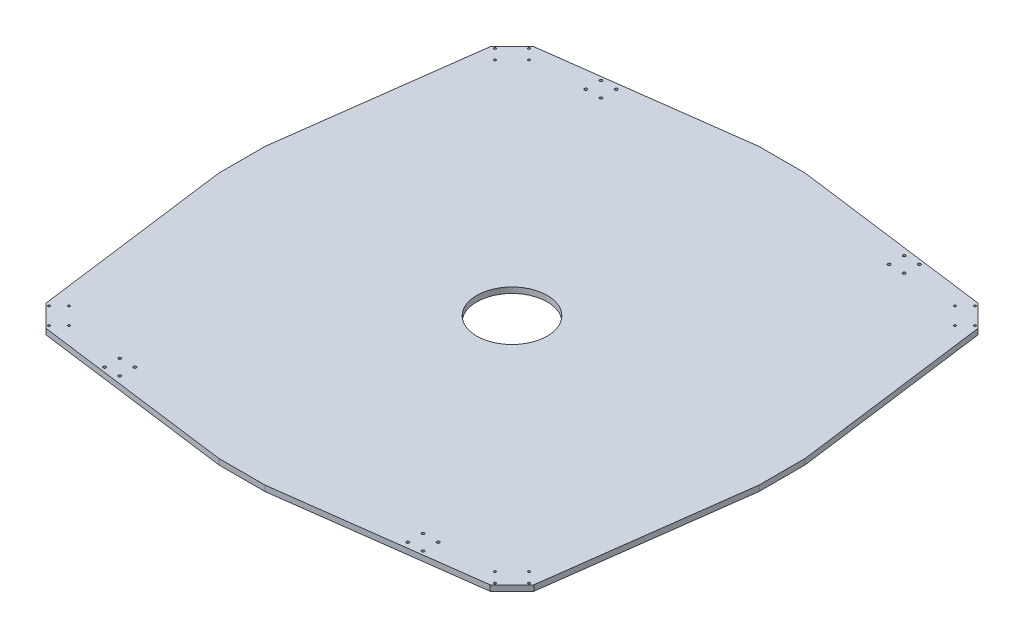
SolidWorks part; units mm, degrees
ref_plane "前视基准面" through (0, 0, 0) normal (0, 0, 1) x (1, 0, 0)
ref_plane "上视基准面" through (0, 0, 0) normal (0, 1, 0) x (1, 0, 0)
ref_plane "右视基准面" through (0, 0, 0) normal (1, 0, 0) x (0, 0, -1)
other "Configuration Table"
sketch "草图1" plane through (0, 0, 0) normal (0, 1, 0) x (1, 0, 0)
  line L0 (-314.9222, 345.9222) -> (-345.9222, 314.9222)
  line L5 (325, -325) -> (-325, 325) construction
  line L6 (325, 325) -> (-325, -325) construction
  line L7 (0, 325) -> (0, -325) construction
  line L8 (-325, 0) -> (325, 0) construction
  line L9 (314.9222, 345.9222) -> (32.7201, 383.0748)
  line L10 (314.9222, 345.9222) -> (345.9222, 314.9222)
  line L12 (-314.9222, 345.9222) -> (-32.7201, 383.0748)
  line L13 (0, 325) -> (0, 399.6983)
  line L14 (-32.7201, 383.0748) -> (32.7201, 383.0748)
  line L15 (314.9222, -345.9222) -> (32.7201, -383.0748)
  line L16 (-32.7201, -383.0748) -> (32.7201, -383.0748)
  line L17 (-314.9222, -345.9222) -> (-32.7201, -383.0748)
  line L18 (-314.9222, -345.9222) -> (-345.9222, -314.9222)
  line L19 (-345.9222, 314.9222) -> (-383.0748, 32.7201)
  line L20 (-383.0748, -32.7201) -> (-383.0748, 32.7201)
  line L21 (-345.9222, -314.9222) -> (-383.0748, -32.7201)
  line L22 (-345.9222, -314.9222) -> (-314.9222, -345.9222)
  line L23 (345.9222, -314.9222) -> (314.9222, -345.9222)
  line L24 (345.9222, -314.9222) -> (383.0748, -32.7201)
  line L25 (383.0748, 32.7201) -> (383.0748, -32.7201)
  line L26 (345.9222, 314.9222) -> (383.0748, 32.7201)
  line L27 (-337.8712, -313.8296) -> (-342.443, -318.4014)
  line L28 (-314.9222, -345.9222) -> (-293.6978, -324.6978)
  line L29 (-326.1795, -302.1379) -> (-298.6587, -329.6587)
  line L30 (-345.9222, -314.9222) -> (-325, -294)
  line L31 (-326.1795, -302.1379) -> (-329.6587, -298.6587)
  line L32 (-313.4871, -289.4455) -> (-337.8712, -313.8296)
  line L33 (-289.4455, -313.4871) -> (-313.8296, -337.8712)
  line L34 (-313.8296, -337.8712) -> (-318.4014, -342.443)
  circle A1 centre (-326.1795, -302.1379) radius 1.5
  circle A2 centre (-302.1379, -326.1795) radius 1.5
  circle A3 centre (-340.3217, -316.28) radius 1.5
  circle A4 centre (-316.28, -340.3217) radius 1.5
  circle A5 centre (0, 0) radius 50
  point P0 (0, 0)
  point P13 (0, 383.0748)
  point P24 (-330.4222, -330.4222)
  point P44 (-326.1795, -302.1379)
  point P45 (-302.1379, -326.1795)
  dimension "D6" = 3
  dimension "D7" = 20
  dimension "D8" = 100
  dimension "D1" = 650
  dimension "D2" = 650
  dimension "D3" = 31
  dimension "D4" = 142.5
  dimension "D5" = 17
extrude "凸台-拉伸2" add sketch "草图1" along normal blind 8 contours L26 L10 L9 L14 L12 L0 L19 L20 L21 L18 L17 L16 L15 L23 L24 L25 | A2 L29 A1 L32 L27 L22 L34 L33 | A1 L31 L30 L22 L27 L32 | A2 L33 L34 L18 L28 L29 region at (-172.4069, 0, -353.7562) region at (-336.0431, 0, 308.3956) region at (-322.2706, 0, 322.2706) region at (-308.3956, 0, 336.0431)
sketch "草图2" plane through (0, 8, 0) normal (0, 1, 0) x (1, 0, 0)
  line L0 (0, 0) -> (-330.4222, -330.4222) construction
pattern_circular "阵列(圆周)1" count 4 over 360 about axis through (0, 8, 0) along (0, 1, 0) of face at (-326.1795, 8, 303.6379) of face at (-340.3217, 8, 317.78) of face at (-302.1379, 8, 327.6795) of face at (-316.28, 8, 341.8217)
sketch "草图3" plane through (0, 8, 0) normal (0, 1, 0) x (1, 0, 0)
  line L0 (383.0748, 0) -> (-381.6237, 0)
  line L1 (383.0748, 32.7201) -> (383.0748, -32.7201) construction
  circle A0 centre (-225.7527, 352.0186) radius 2
  circle A1 centre (-204.2473, 352.0186) radius 2
  circle A2 centre (-225.7527, 330.5131) radius 2
  circle A3 centre (-204.2473, 330.5131) radius 2
  circle A4 centre (204.2473, 352.0186) radius 2
  circle A5 centre (225.7527, 352.0186) radius 2
  circle A6 centre (204.2473, 330.5131) radius 2
  circle A7 centre (225.7429, 330.3998) radius 2
  circle A8 centre (225.7429, -330.3998) radius 2
  circle A9 centre (204.2473, -330.5131) radius 2
  circle A10 centre (225.7527, -352.0186) radius 2
  circle A11 centre (204.2473, -352.0186) radius 2
  circle A12 centre (-204.2473, -330.5131) radius 2
  circle A13 centre (-225.7527, -330.5131) radius 2
  circle A14 centre (-204.2473, -352.0186) radius 2
  circle A15 centre (-225.7527, -352.0186) radius 2
  dimension "D1" = 4
extrude "切除-拉伸1" cut sketch "草图3" against normal blind 55 and the other way blind 37 contours A13 | A15 | A12 | A14 | A10 | A9 | A11 | A8 | A2 | A0 | A3 | A1 | A7 | A5 | A6 | A4 region at (-225.7527, 8, -352.0186) region at (-204.2473, 8, -352.0186) region at (-225.7527, 8, -330.5131) region at (-204.2473, 8, -330.5131) region at (204.2473, 8, -352.0186) region at (225.7527, 8, -352.0186) region at (204.2473, 8, -330.5131) region at (225.7429, 8, -330.3998) region at (225.7429, 8, 330.3998) region at (204.2473, 8, 330.5131) region at (225.7527, 8, 352.0186) region at (204.2473, 8, 352.0186) region at (-204.2473, 8, 330.5131) region at (-225.7527, 8, 330.5131) region at (-204.2473, 8, 352.0186) region at (-225.7527, 8, 352.0186)
